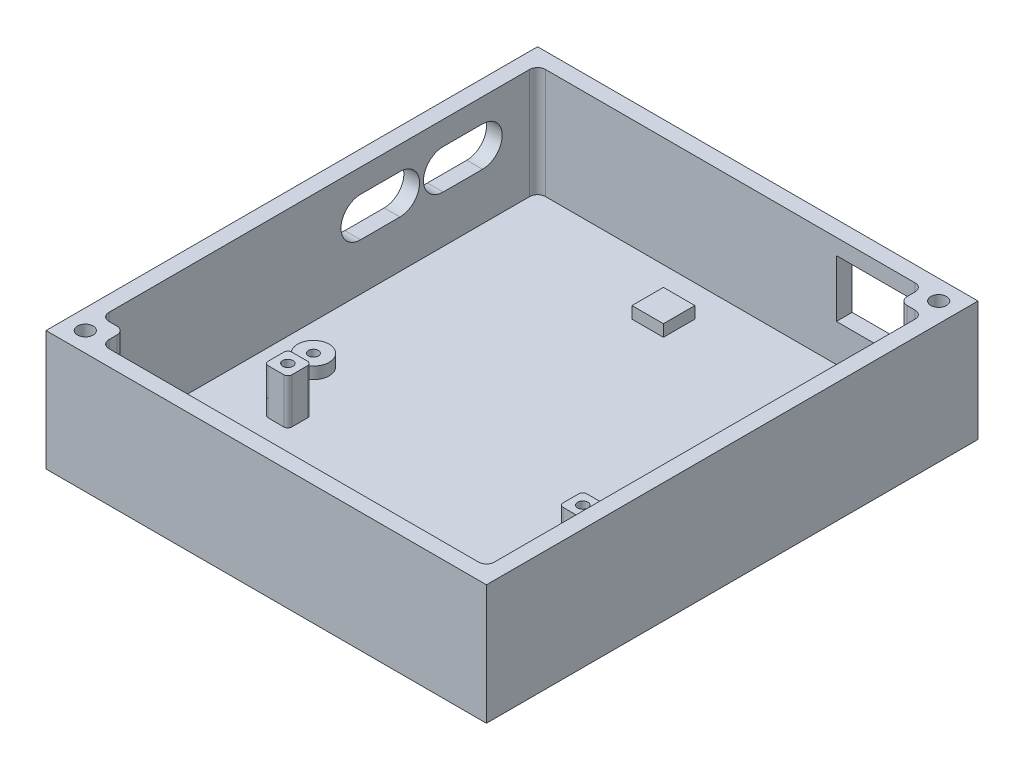
SolidWorks part; units mm, degrees
ref_plane "Front Plane" through (0, 0, 0) normal (0, 0, 1) x (1, 0, 0)
ref_plane "Top Plane" through (0, 0, 0) normal (0, 1, 0) x (1, 0, 0)
ref_plane "Right Plane" through (0, 0, 0) normal (1, 0, 0) x (0, 0, -1)
sketch "Sketch1" plane through (0, 0, 0) normal (0, 1, 0) x (1, 0, 0)
  line L1 (-56, -62.5) -> (56, -62.5)
  line L2 (-56, -62.5) -> (-56, 62.5)
  line L3 (-56, 62.5) -> (56, 62.5)
  line L4 (56, -62.5) -> (56, 62.5)
  line L5 (-56, -62.5) -> (56, 62.5) construction
  line L6 (-56, 62.5) -> (56, -62.5) construction
  point P0 (0, 0)
  dimension "D1" = 112
  dimension "D2" = 125
extrude "Boss-Extrude1" add sketch "Sketch1" along normal blind 2.5
sketch "Sketch2" plane through (0, 2.5, 0) normal (0, 1, 0) x (1, 0, 0)
  line L0 (-56, -62.5) -> (56, -62.5) construction
  line L1 (-12, 50.5) -> (-4, 50.5) construction
  line L2 (-12, 50.5) -> (-12, 42.5) construction
  line L3 (-12, 42.5) -> (-4, 42.5) construction
  line L4 (52, 52.5) -> (46, 52.5)
  line L5 (-4, 50.5) -> (-4, 42.5) construction
  line L6 (-56, 62.5) -> (-56, -62.5) construction
  line L7 (46, 52.5) -> (46, 58.5)
  line L8 (52, -58.5) -> (52, 58.5)
  line L9 (52, 58.5) -> (-52, 58.5)
  line L10 (-52, 58.5) -> (-52, -58.5)
  line L11 (-52, -58.5) -> (52, -58.5)
  line L12 (52, -58.5) -> (52, 52.5)
  line L13 (46, 58.5) -> (-52, 58.5)
  line L14 (-52, 58.5) -> (-52, -52.5)
  line L15 (-46, -58.5) -> (52, -58.5)
  line L16 (56, 62.5) -> (-56, 62.5) construction
  line L29 (-46, -58.5) -> (-46, -52.5)
  line L30 (-46, -52.5) -> (-52, -52.5)
  line L31 (56, -62.5) -> (56, 62.5) construction
  circle A0 centre (-42, -8.5) radius 1.25 construction
  circle A1 centre (38, -8.5) radius 1.25 construction
  circle A2 centre (-51, -57.5) radius 2
  circle A3 centre (51, 57.5) radius 2
  line M12 (56, -62.5) -> (56, 62.5)
  line M13 (56, 62.5) -> (-56, 62.5)
  line M14 (-56, 62.5) -> (-56, -62.5)
  line M15 (-56, -62.5) -> (56, -62.5)
  dimension "D1" = 2.5
  dimension "D15" = 4
  dimension "D18" = 5
  dimension "D2" = 80
  dimension "D3" = 6
  dimension "D5" = 8
  dimension "D6" = 67
  dimension "D8" = 14
  dimension "D9" = 8
  dimension "D10" = 8
  dimension "D11" = 40
  dimension "D12" = 5
  dimension "D16" = 5
  dimension "D17" = 5
  dimension "D4" = 4
extrude "Boss-Extrude2" add sketch "Sketch2" along normal blind 10 contours A0 | A1 | A3 A2 L29 L30 L14 L13 L7 L4 L12 L15 M15 M12 M13 M14 region at (48.5409, 2.5, -55.0409) region at (-48.5409, 2.5, 55.0409) region at (0, 2.5, 60.8216)
sketch "Sketch3" plane through (0, 2.5, 0) normal (0, 1, 0) x (1, 0, 0)
  line L0 (-31.5, -50.5) -> (-31.5, -25.5) construction
  line L1 (-34.5, -53.5) -> (40.5, -53.5) construction
  line L2 (-34.5, -53.5) -> (-34.5, -22.5) construction
  line L3 (-34.5, -22.5) -> (40.5, -22.5) construction
  line L4 (40.5, -53.5) -> (40.5, -22.5) construction
  line L5 (-31.5, -25.5) -> (37.5, -25.5) construction
  line L6 (37.5, -50.5) -> (37.5, -25.5) construction
  line L7 (-31.5, -50.5) -> (37.5, -50.5) construction
  line L8 (-37.5, -19.5) -> (43.5, -19.5)
  line L9 (43.5, -56.5) -> (43.5, -19.5)
  line L10 (-37.5, -56.5) -> (43.5, -56.5)
  line L11 (-37.5, -56.5) -> (-37.5, -19.5)
  line L12 (-46, -58.5) -> (52, -58.5) construction
  line L13 (-46, -58.5) -> (52, -58.5) construction
  line L14 (-31.5, -25.5) -> (-37.5, -25.5)
  line L15 (-31.5, -50.5) -> (-37.5, -50.5)
  line L16 (37.5, -25.5) -> (43.5, -25.5)
  line L17 (37.5, -50.5) -> (43.5, -50.5)
  line L18 (37.5, -25.5) -> (37.5, -19.5)
  line L19 (37.5, -50.5) -> (37.5, -56.5)
  line L20 (-31.5, -50.5) -> (-31.5, -56.5)
  line L21 (-31.5, -19.5) -> (-31.5, -25.5)
  circle A0 centre (-34.5, -22.5) radius 1.3
  circle A1 centre (40.5, -22.5) radius 1.3
  circle A2 centre (40.5, -53.5) radius 1.3
  circle A3 centre (-34.5, -53.5) radius 1.3
  point P17 (3, -22.5)
  point P19 (3, -58.5)
  dimension "D3" = 2.6
  dimension "D4" = 75
  dimension "D5" = 31
  dimension "D6" = 5
  dimension "D1" = 3
  dimension "D2" = 3
extrude "Boss-Extrude3" add sketch "Sketch3" along normal blind 11.5 contours L20 L15 L11 L10 A3 | L21 L8 L11 L14 A0 | L18 L16 L9 L8 A1 | L17 L19 L10 L9 A2 region at (-34.5, 2.5, 19.5849) region at (40.5, 2.5, 19.5849) region at (-34.5, 2.5, 50.5849) region at (43.4151, 2.5, 53.5)
sketch "Sketch5" plane through (0, 2.5, 0) normal (0, 1, 0) x (1, 0, 0)
  line L0 (-4, 50.5) -> (-4, 42.5) construction
  line L1 (-12, 50.5) -> (-4, 50.5) construction
  line L2 (-12, 50.5) -> (-12, 42.5) construction
  line L3 (-12, 42.5) -> (-4, 42.5) construction
  line L4 (-4, 50.5) -> (-4, 42.5)
  line L5 (-12, 50.5) -> (-4, 50.5)
  line L6 (-12, 50.5) -> (-12, 42.5)
  line L7 (-12, 42.5) -> (-4, 42.5)
  circle A0 centre (-42, -8.5) radius 4
  circle A1 centre (38, -8.5) radius 4
  circle A2 centre (38, -8.5) radius 1.25 construction
  circle A3 centre (38, -8.5) radius 1.25
  circle A4 centre (-42, -8.5) radius 1.25 construction
  circle A5 centre (-42, -8.5) radius 1.25
  dimension "D1" = 8
extrude "Boss-Extrude4" add sketch "Sketch5" along normal blind 3
sketch "Sketch6" plane through (0, 14, 0) normal (0, 1, 0) x (1, 0, 0)
  line L4 (-31.5, -56.5) -> (-31.5, -50.5)
  line L5 (-31.5, -50.5) -> (-37.5, -50.5)
  line L6 (-37.5, -50.5) -> (-37.5, -56.5)
  line L7 (-37.5, -56.5) -> (-31.5, -56.5)
  line L8 (-31.5, -56.5) -> (-31.5, -50.5)
  line L9 (-31.5, -50.5) -> (-37.5, -50.5)
  line L10 (-37.5, -50.5) -> (-37.5, -56.5)
  line L11 (-37.5, -56.5) -> (-31.5, -56.5)
  line L12 (37.5, -19.5) -> (37.5, -25.5)
  line L13 (37.5, -25.5) -> (43.5, -25.5)
  line L14 (43.5, -25.5) -> (43.5, -19.5)
  line L15 (43.5, -19.5) -> (37.5, -19.5)
  line L16 (37.5, -19.5) -> (37.5, -25.5)
  line L17 (37.5, -25.5) -> (43.5, -25.5)
  line L18 (43.5, -25.5) -> (43.5, -19.5)
  line L19 (43.5, -19.5) -> (37.5, -19.5)
  line L20 (43.5, -50.5) -> (37.5, -50.5)
  line L21 (37.5, -50.5) -> (37.5, -56.5)
  line L22 (37.5, -56.5) -> (43.5, -56.5)
  line L23 (43.5, -56.5) -> (43.5, -50.5)
  line L24 (43.5, -50.5) -> (37.5, -50.5)
  line L25 (37.5, -50.5) -> (37.5, -56.5)
  line L26 (37.5, -56.5) -> (43.5, -56.5)
  line L27 (43.5, -56.5) -> (43.5, -50.5)
  circle A0 centre (40.5, -53.5) radius 1.3 construction
  circle A1 centre (40.5, -22.5) radius 1.3
  circle A2 centre (40.5, -22.5) radius 1.3
  circle A3 centre (-34.5, -53.5) radius 1.3 construction
  circle A4 centre (40.5, -53.5) radius 1.3
  circle A5 centre (-34.5, -53.5) radius 1.3
  dimension "D1" = 0
  dimension "D2" = 0
  dimension "D3" = 0
  dimension "D4" = 0
extrude "Boss-Extrude5" add sketch "Sketch6" along normal blind 6.3
sketch "Sketch7" plane through (0, 12.5, 0) normal (0, 1, 0) x (1, 0, 0)
  line L4 (-56, -62.5) -> (56, -62.5)
  line L5 (56, -62.5) -> (56, 62.5)
  line L6 (56, 62.5) -> (-56, 62.5)
  line L7 (-56, 62.5) -> (-56, -62.5)
  line L8 (-56, -62.5) -> (56, -62.5)
  line L9 (56, -62.5) -> (56, 62.5)
  line L10 (56, 62.5) -> (-56, 62.5)
  line L11 (-56, 62.5) -> (-56, -62.5)
  circle M5 centre (51, 57.5) radius 2
  line M6 (46, 52.5) -> (52, 52.5)
  line M7 (52, 52.5) -> (52, -58.5)
  line M13 (52, 52.5) -> (52, -58.5)
  line M14 (52, -58.5) -> (-46, -58.5)
  line M15 (-46, -58.5) -> (-46, -52.5)
  line M16 (-46, -52.5) -> (-52, -52.5)
  line M17 (-52, -52.5) -> (-52, 58.5)
  line M18 (-52, 58.5) -> (46, 58.5)
  line M19 (46, 58.5) -> (46, 52.5)
  circle M22 centre (-51, -57.5) radius 2
  line M23 (-56, -62.5) -> (56, -62.5)
  line M24 (56, -62.5) -> (56, 62.5)
  line M25 (56, 62.5) -> (-56, 62.5)
  line M26 (-56, 62.5) -> (-56, -62.5)
  dimension "D1" = 0
extrude "Boss-Extrude6" add sketch "Sketch7" along normal blind 18 contours M26 M23 M24 M25 M22 M5 M7 M13 M14 M15 M16 M17 M18 M19 M6 region at (-54.3216, 12.5, 0)
sketch "Sketch9" plane through (-56, 0, 0) normal (-1, 0, 0) x (0, 0, 1)
  line L0 (-44.5, 19.5) -> (-34.5, 19.5) construction
  line L1 (-44.5, 24.5) -> (-34.5, 24.5)
  line L2 (-44.5, 14.5) -> (-34.5, 14.5)
  line L3 (-23.5, 19.5) -> (-13.5, 19.5) construction
  line L4 (-23.5, 24.5) -> (-13.5, 24.5)
  line L5 (-23.5, 14.5) -> (-13.5, 14.5)
  line L9 (-62.5, 30.5) -> (62.5, 30.5) construction
  line L10 (-62.5, 30.5) -> (-62.5, 0) construction
  arc A0 (-44.5, 24.5) -> (-44.5, 14.5) centre (-44.5, 19.5) ccw
  arc A1 (-34.5, 14.5) -> (-34.5, 24.5) centre (-34.5, 19.5) ccw
  arc A2 (-23.5, 24.5) -> (-23.5, 14.5) centre (-23.5, 19.5) ccw
  arc A3 (-13.5, 14.5) -> (-13.5, 24.5) centre (-13.5, 19.5) ccw
  point P2 (-39.5, 19.5)
  point P8 (-18.5, 19.5)
  point P23 (-29.5, 19.5)
  point P24 (-49.5, 19.5)
  dimension "D2" = 5
  dimension "D1" = 11
  dimension "D3" = 20
  dimension "D4" = 18
  dimension "D5" = 39
extrude "Cut-Extrude1" cut sketch "Sketch9" against normal up to next
sketch "Sketch10" plane through (0, 0, -62.5) normal (0, 0, -1) x (-1, 0, 0)
  line L3 (-24, 12) -> (-42, 12)
  line L5 (-56, 30.5) -> (-56, 0) construction
  line L6 (-42, 26.5) -> (-24, 26.5)
  line L7 (-42, 26.5) -> (-42, 12)
  line L8 (-24, 12) -> (-24, 26.5)
  line L9 (-56, 30.5) -> (56, 30.5) construction
  line L10 (-56, 0) -> (56, 0) construction
  point P8 (-33, 12)
  dimension "D1" = 14
  dimension "D2" = 23
  dimension "D3" = 18
  dimension "D4" = 4
  dimension "D5" = 12
extrude "Cut-Extrude2" cut sketch "Sketch10" against normal up to next
fillet "Fillet1" radius 2 8 edges at (-46, 16.5, 52.5) (46, 16.5, -52.5) (52, 16.5, 58.5) (-52, 16.5, -58.5) (-46, 16.5, 58.5) (-52, 16.5, 52.5) (52, 16.5, -52.5) (46, 16.5, -58.5)
fillet "Fillet3" radius 1 16 edges at (43.5, 11.4, 25.5) (43.5, 11.4, 56.5) (-31.5, 11.4, 56.5) (-31.5, 11.4, 50.5) (-37.5, 11.4, 50.5) (-37.5, 11.4, 56.5) (37.5, 11.4, 56.5) (37.5, 11.4, 50.5) (43.5, 11.4, 50.5) (37.5, 11.4, 25.5) (43.5, 11.4, 19.5) (37.5, 11.4, 19.5) (-31.5, 8.25, 19.5) (-37.5, 8.25, 19.5) (-37.5, 8.25, 25.5) (-31.5, 8.25, 25.5)
